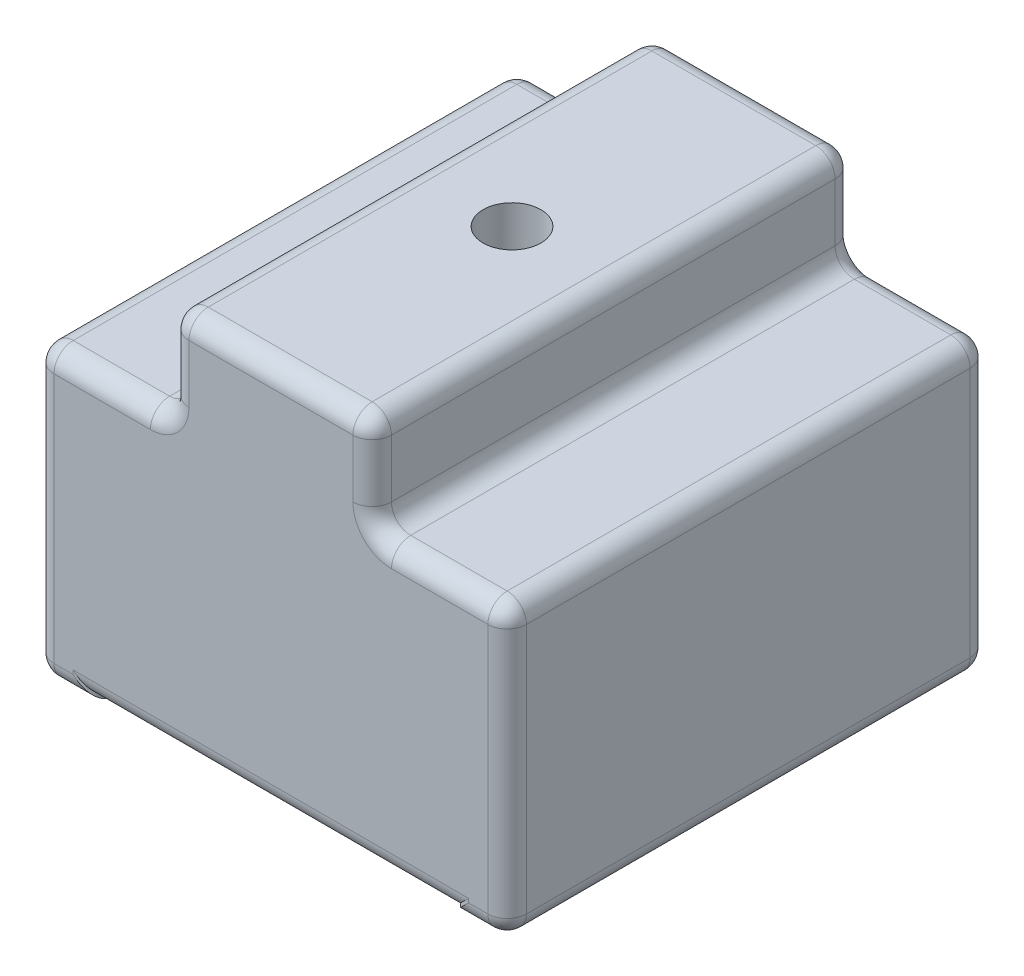
SolidWorks part; units mm, degrees
ref_plane "Front Plane" through (0, 0, 0) normal (0, 0, 1) x (1, 0, 0)
ref_plane "Top Plane" through (0, 0, 0) normal (0, 1, 0) x (1, 0, 0)
ref_plane "Right Plane" through (0, 0, 0) normal (1, 0, 0) x (0, 0, -1)
sketch "Sketch2" plane through (0, 0, 0) normal (0, 0, 1) x (1, 0, 0)
  line L0 (0, 0) -> (0, 38.1)
  line L1 (0, 38.1) -> (17.78, 38.1)
  line L2 (17.78, 38.1) -> (17.78, 50.8)
  line L3 (17.78, 50.8) -> (44.45, 50.8)
  line L4 (44.45, 50.8) -> (44.45, 38.1)
  line L5 (44.45, 38.1) -> (62.23, 38.1)
  line L6 (62.23, 38.1) -> (62.23, 0)
  line L8 (54.61, 0) -> (62.23, 0)
  line L9 (54.61, 0) -> (54.61, 0.508)
  line L10 (54.61, 0.508) -> (7.62, 0.508)
  line L11 (7.62, 0.508) -> (7.62, 0)
  line L12 (7.62, 0) -> (0, 0)
  dimension "D1" = 38.1
  dimension "D2" = 12.7
  dimension "D3" = 12.7
  dimension "D4" = 17.78
  dimension "D5" = 17.78
  dimension "D6" = 7.62
  dimension "D7" = 7.62
  dimension "D8" = 46.99
  dimension "D9" = 0.508
  dimension "D10" = 38.1
extrude "Boss-Extrude1" add sketch "Sketch2" along normal blind 58.42
sketch "Sketch3" plane through (0, 0.508, 0) normal (0, -1, 0) x (1, 0, 0)
  line L0 (7.62, 58.42) -> (54.61, 58.42) construction
  line L1 (7.62, 0) -> (54.61, 0) construction
  line L2 (7.62, 58.42) -> (7.62, 0) construction
  line L3 (54.61, 58.42) -> (54.61, 0) construction
  line L12 (10.16, 3.81) -> (52.07, 3.81)
  line L13 (52.07, 3.81) -> (52.07, 54.61)
  line L14 (52.07, 54.61) -> (10.16, 54.61)
  line L15 (10.16, 54.61) -> (10.16, 3.81)
  dimension "D1" = 3.81
  dimension "D2" = 3.81
  dimension "D3" = 2.54
  dimension "D4" = 2.54
extrude "Cut-Extrude1" cut sketch "Sketch3" against normal blind 2.54
sketch "Sketch15" plane through (0, 0.508, 0) normal (0, -1, 0) x (-1, 0, 0)
  line L0 (-52.07, -29.21) -> (-10.16, -29.21) construction
  line L1 (-52.07, -3.81) -> (-52.07, -54.61) construction
  line L2 (-10.16, -54.61) -> (-10.16, -3.81) construction
  line L3 (-52.07, -29.21) -> (-52.07, -54.61)
  line L4 (-52.07, -54.61) -> (-10.16, -54.61)
  line L6 (-10.16, -54.61) -> (-10.16, -29.21)
  line L7 (-10.16, -3.81) -> (-52.07, -3.81) construction
  line L8 (-52.07, -54.61) -> (-10.16, -54.61) construction
  line L9 (-52.07, -29.21) -> (-10.16, -29.21)
  dimension "D1" = 0
revolve "Cut-Revolve2" cut sketch "Sketch15" angle 360 about L0
sketch "Sketch17" plane through (0, 0.508, 0) normal (0, -1, 0) x (1, 0, 0)
  line L0 (52.07, 3.81) -> (52.07, 54.61) construction
  line L1 (46.99, 1.27) -> (15.24, 1.27)
  line L2 (46.99, 1.27) -> (46.99, 29.21)
  line L3 (46.99, 29.21) -> (15.24, 29.21)
  line L4 (15.24, 1.27) -> (15.24, 29.21)
  line L5 (7.62, 58.42) -> (7.62, 0) construction
  line L6 (54.61, 58.42) -> (54.61, 0) construction
  line L7 (7.62, 0) -> (54.61, 0) construction
  point P12 (52.07, 29.21)
  dimension "D1" = 0
  dimension "D2" = 7.62
  dimension "D3" = 7.62
  dimension "D4" = 1.27
revolve "Cut-Revolve3" cut sketch "Sketch17" angle 230 about L3 other way angle 20
sketch "Sketch18" plane through (0, 0.508, 0) normal (0, -1, 0) x (1, 0, 0)
  line L0 (10.16, 3.81) -> (15.24, 3.81) construction
  line L1 (52.07, 29.21) -> (46.99, 29.21)
  line L2 (52.07, 29.21) -> (52.07, 47.752)
  line L3 (52.07, 47.752) -> (46.99, 47.752)
  line L4 (46.99, 29.21) -> (46.99, 47.752)
  line L5 (10.16, 47.752) -> (15.24, 47.752)
  line L6 (10.16, 47.752) -> (10.16, 29.21)
  line L7 (10.16, 29.21) -> (15.24, 29.21)
  line L8 (15.24, 47.752) -> (15.24, 29.21)
  line L33 (52.07, 3.81) -> (52.07, 54.61) construction
  line L34 (10.16, 29.21) -> (52.07, 29.21) construction
  line L35 (10.16, 54.61) -> (52.07, 54.61) construction
  line L36 (15.24, 57.15) -> (15.24, 54.61) construction
  line L38 (46.99, 54.61) -> (46.99, 57.15) construction
  line L41 (10.16, 47.752) -> (7.62, 47.752)
  line L42 (10.16, 47.752) -> (10.16, 44.196)
  line L43 (10.16, 44.196) -> (7.62, 44.196)
  line L44 (7.62, 47.752) -> (7.62, 44.196)
  line L45 (10.16, 54.61) -> (15.24, 54.61) construction
  line L46 (52.07, 47.752) -> (54.61, 47.752)
  line L47 (52.07, 47.752) -> (52.07, 44.196)
  line L48 (52.07, 44.196) -> (54.61, 44.196)
  line L49 (54.61, 47.752) -> (54.61, 44.196)
  line L51 (10.16, 54.61) -> (10.16, 3.81) construction
  point P34 (12.7, 3.81)
  dimension "D1" = 25.4
  dimension "D2" = 6.858
  dimension "D3" = 3.556
  dimension "D4" = 6.858
  dimension "D5" = 2.54
  dimension "D6" = 0
  dimension "D7" = 3.556
  dimension "D8" = 2.54
sketch "Sketch19" plane through (0, 0, 0) normal (0, 0, -1) x (-1, 0, 0)
  line L24 (-7.62, 0) -> (0, 0)
  line L25 (0, 0) -> (0, 38.1)
  line L26 (0, 38.1) -> (-17.78, 38.1)
  line L27 (-17.78, 38.1) -> (-17.78, 50.8)
  line L28 (-17.78, 50.8) -> (-44.45, 50.8)
  line L29 (-44.45, 50.8) -> (-44.45, 38.1)
  line L30 (-44.45, 38.1) -> (-62.23, 38.1)
  line L31 (-62.23, 38.1) -> (-62.23, 0)
  line L32 (-62.23, 0) -> (-54.61, 0)
  line L33 (-54.61, 0) -> (-54.61, 0.508)
  line L34 (-54.61, 0.508) -> (-7.62, 0.508)
  line L35 (-7.62, 0.508) -> (-7.62, 0)
  line L36 (-7.62, 0) -> (0, 0)
  line L37 (0, 0) -> (0, 38.1)
  line L38 (0, 38.1) -> (-17.78, 38.1)
  line L39 (-17.78, 38.1) -> (-17.78, 50.8)
  line L40 (-17.78, 50.8) -> (-44.45, 50.8)
  line L41 (-44.45, 50.8) -> (-44.45, 38.1)
  line L42 (-44.45, 38.1) -> (-62.23, 38.1)
  line L43 (-62.23, 38.1) -> (-62.23, 0)
  line L44 (-62.23, 0) -> (-54.61, 0)
  line L45 (-54.61, 0) -> (-54.61, 0.508)
  line L46 (-54.61, 0.508) -> (-7.62, 0.508)
  line L47 (-7.62, 0.508) -> (-7.62, 0)
  dimension "D1" = 0
extrude "Boss-Extrude2" add sketch "Sketch19" along normal blind 2.54
sketch "Sketch20" plane through (0, 0, 58.42) normal (0, 0, 1) x (1, 0, 0)
  line L24 (0, 0) -> (7.62, 0)
  line L25 (7.62, 0) -> (7.62, 0.508)
  line L26 (7.62, 0.508) -> (54.61, 0.508)
  line L27 (54.61, 0.508) -> (54.61, 0)
  line L28 (54.61, 0) -> (62.23, 0)
  line L29 (62.23, 0) -> (62.23, 38.1)
  line L30 (62.23, 38.1) -> (44.45, 38.1)
  line L31 (44.45, 38.1) -> (44.45, 50.8)
  line L32 (44.45, 50.8) -> (17.78, 50.8)
  line L33 (17.78, 50.8) -> (17.78, 38.1)
  line L34 (17.78, 38.1) -> (0, 38.1)
  line L35 (0, 38.1) -> (0, 0)
  line L36 (0, 0) -> (7.62, 0)
  line L37 (7.62, 0) -> (7.62, 0.508)
  line L38 (7.62, 0.508) -> (54.61, 0.508)
  line L39 (54.61, 0.508) -> (54.61, 0)
  line L40 (54.61, 0) -> (62.23, 0)
  line L41 (62.23, 0) -> (62.23, 38.1)
  line L42 (62.23, 38.1) -> (44.45, 38.1)
  line L43 (44.45, 38.1) -> (44.45, 50.8)
  line L44 (44.45, 50.8) -> (17.78, 50.8)
  line L45 (17.78, 50.8) -> (17.78, 38.1)
  line L46 (17.78, 38.1) -> (0, 38.1)
  line L47 (0, 38.1) -> (0, 0)
  dimension "D1" = 0
extrude "Boss-Extrude3" add sketch "Sketch20" along normal blind 2.54
revolve "Cut-Revolve4" cut sketch "Sketch18" angle 340 about L34 region at (49.53, 0.508, 38.481) region at (12.7, 0.508, 38.481) region at (8.89, 0.508, 45.974)
fillet "Fillet2" radius 2.54 32 edges at (62.23, 0, 29.21) (62.23, 38.1, 29.21) (44.45, 38.1, 29.21) (0, 0, 29.21) (0, 38.1, 29.21) (17.78, 38.1, 29.21) (44.45, 50.8, 29.21) (17.78, 50.8, 29.21) (53.34, 38.1, 60.96) (53.34, 38.1, -2.54) (62.23, 19.05, 60.96) (62.23, 19.05, -2.54) (44.45, 44.45, 60.96) (44.45, 44.45, -2.54) (0, 19.05, 60.96) (0, 19.05, -2.54) (8.89, 38.1, 60.96) (8.89, 38.1, -2.54) (17.78, 44.45, 60.96) (17.78, 44.45, -2.54) (31.115, 50.8, 60.96) (31.115, 50.8, -2.54) (58.42, 0, -2.54) (54.61, 0.254, -2.54) (31.115, 0.508, -2.54) (7.62, 0.254, -2.54) (3.81, 0, -2.54) (54.61, 0.254, 60.96) (3.81, 0, 60.96) (7.62, 0.254, 60.96) (31.115, 0.508, 60.96) (58.42, 0, 60.96)
sketch "Sketch25" plane through (0, 0, 0) normal (0, -1, 0) x (1, 0, 0)
  line L0 (7.62, 29.21) -> (31.115, 29.21) construction
  line L1 (7.62, 58.42) -> (7.62, 0) construction
  line L2 (5.08, 60.96) -> (57.15, 60.96) construction
  line L4 (20.32, 0) -> (20.32, 58.42) construction
  circle A0 centre (31.115, 29.21) radius 3.81
  dimension "D2" = 7.62
  dimension "D3" = 10.795
  dimension "D1" = 31.75
extrude "Cut-Extrude2" cut sketch "Sketch25" against normal blind 66.294
sketch "Sketch26" plane through (0, 0, 0) normal (0, 1, 0) x (1, 0, 0)
  line L0 (31.115, -29.21) -> (31.115, -24.13) construction
  line L1 (27.305, -29.21) -> (27.305, -24.13)
  line L2 (34.925, -29.21) -> (34.925, -24.13)
  arc A0 (27.305, -29.21) -> (34.925, -29.21) centre (31.115, -29.21) ccw
  arc A1 (34.925, -24.13) -> (27.305, -24.13) centre (31.115, -24.13) ccw
  circle A2 centre (31.115, -29.21) radius 3.81 construction
  point P2 (31.115, -26.67)
  dimension "D3" = 3.81
  dimension "D1" = 0
  dimension "D2" = 0
  dimension "D4" = 5.08
extrude "Cut-Extrude3" cut sketch "Sketch26" along normal blind 30.48
chamfer "Chamfer1" distance 5.08 angle 63 1 edges at (31.115, 30.48, 25.4) first distance on face at (31.115, 30.48, 24.765)
fillet "Fillet6" radius 12.7 1 edges at (31.115, 40.4501, 25.4)
fillet "Fillet7" radius 5.08 4 edges at (27.305, 25.7794, 26.6571) (31.9683, 25.6351, 25.4968) (34.925, 25.7794, 26.6571) (31.6508, 24.3156, 20.3579)
